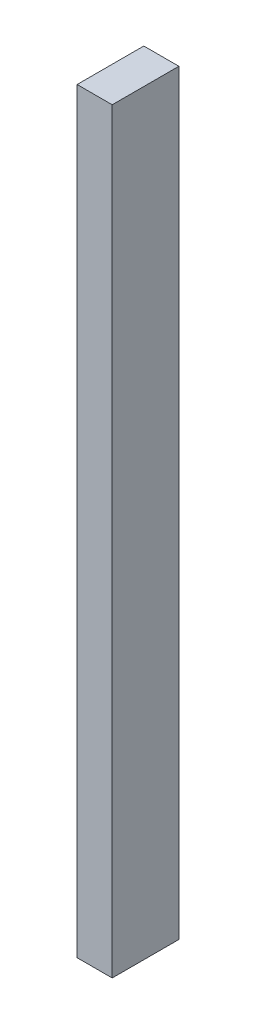
SolidWorks part; units mm, degrees
ref_plane "Front Plane" through (0, 0, 0) normal (0, 0, 1) x (1, 0, 0)
ref_plane "Top Plane" through (0, 0, 0) normal (0, 1, 0) x (1, 0, 0)
ref_plane "Right Plane" through (0, 0, 0) normal (1, 0, 0) x (0, 0, -1)
sketch "Sketch1" plane through (0, 0, 0) normal (0, 1, 0) x (1, 0, 0)
  line L1 (0, 0) -> (5.08, 0)
  line L2 (0, 0) -> (0, 9.652)
  line L3 (0, 9.652) -> (5.08, 9.652)
  line L4 (5.08, 0) -> (5.08, 9.652)
  dimension "D1" = 5.08
  dimension "D2" = 9.652
extrude "Boss-Extrude1" add sketch "Sketch1" along normal blind 109.474
